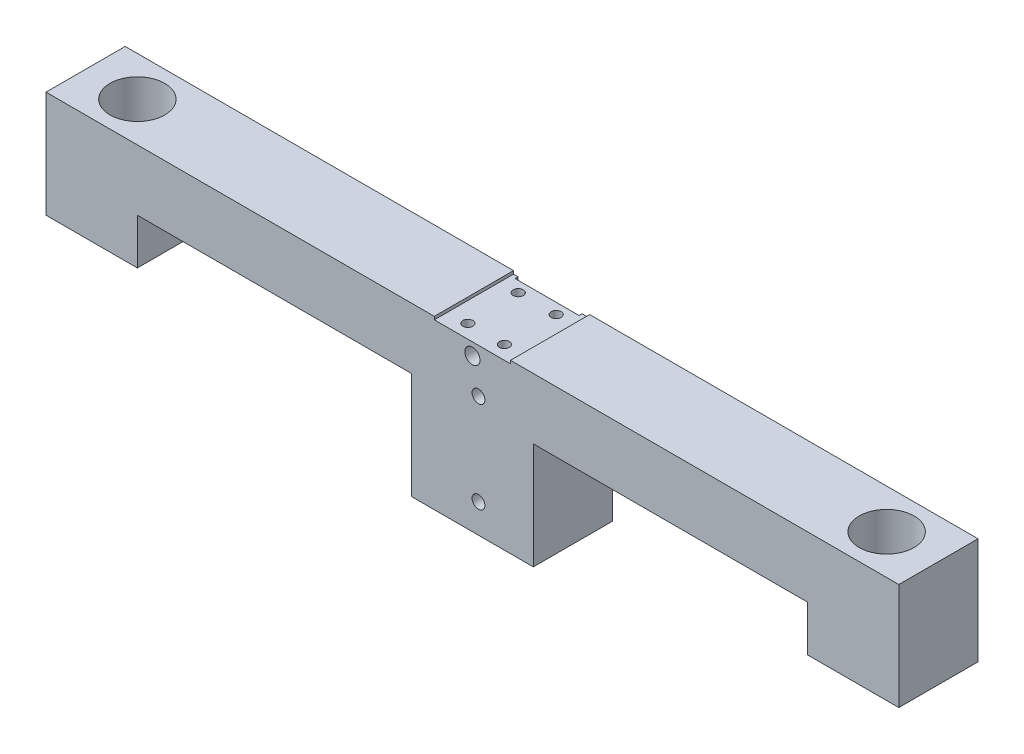
SolidWorks part; units mm, degrees
ref_plane "前视基准面" through (0, 0, 0) normal (0, 0, 1) x (1, 0, 0)
ref_plane "上视基准面" through (0, 0, 0) normal (0, 1, 0) x (1, 0, 0)
ref_plane "右视基准面" through (0, 0, 0) normal (1, 0, 0) x (0, 0, -1)
sketch "草图1" plane through (0, 0, 0) normal (0, 0, 1) x (1, 0, 0)
  line L1 (0, 0) -> (280, 0)
  line L2 (0, 0) -> (0, 35)
  line L3 (0, 35) -> (280, 35)
  line L4 (280, 0) -> (280, 35)
  dimension "D1" = 280
  dimension "D2" = 35
extrude "凸台-拉伸1" add sketch "草图1" along normal blind 26
sketch "草图3" plane through (0, 0, 0) normal (0, -1, 0) x (1, 0, 0)
  line L0 (0, 13) -> (280, 13) construction
  line L1 (0, 26) -> (0, 0) construction
  line L2 (280, 26) -> (280, 0) construction
  line L3 (280, 13) -> (140, 13) construction
  line L4 (140, 13) -> (140, -29.0433) construction
  circle A0 centre (17, 13) radius 9
  circle A1 centre (263, 13) radius 9
  dimension "D1" = 18
  dimension "D2" = 246
extrude "切除-拉伸1" cut sketch "草图3" against normal through all
sketch "草图4" plane through (0, 35, 0) normal (0, 1, 0) x (1, 0, 0)
  line L0 (140, -26) -> (140, 0) construction
  line L1 (280, -26) -> (0, -26) construction
  line L2 (280, 0) -> (0, 0) construction
  line L4 (152.5, -26) -> (127.5, -26)
  line L5 (152.5, -26) -> (152.5, 0)
  line L6 (152.5, 0) -> (127.5, 0)
  line L7 (127.5, -26) -> (127.5, 0)
  dimension "D1" = 25
extrude "切除-拉伸2" cut sketch "草图4" against normal blind 1
hole_wizard "M4 螺纹孔1" positions "草图5" profile "草图6" tap size "M4" standard "ISO"
sketch "草图5" plane through (0, 34, 0) normal (0, 1, 0) x (1, 0, 0)
  point P0 (146, -21.5)
  point P3 (134, -21.5)
  point P6 (146, -4.5)
  point P9 (133.547, -4.5)
sketch "草图6" plane through (146, 34, 21.5) normal (1, 0, 0) x (0, 0, 1)
  line L0 (0, 0) -> (0, 11.0914)
  line L1 (0, 11.0914) -> (1.65, 10.1)
  line L2 (1.65, 10.1) -> (1.65, 0)
  line L5 (1.65, 0) -> (0, 0)
  line L10 (0, 11.0914) -> (-1.65, 10.1) construction
  line L11 (0, -6.35) -> (0, 107.95) construction
  dimension "螺纹孔钻头直径" = 3.3
  dimension "螺纹孔钻头深度" = 10.1
  dimension "导头角度" = 118
cosmetic thread "孔螺蚊线1" parameters "D1"=8, "D2"=4
cosmetic thread "孔螺蚊线2" parameters "D1"=8, "D2"=4
cosmetic thread "孔螺蚊线3" parameters "D1"=8, "D2"=4
cosmetic thread "孔螺蚊线4" parameters "D1"=8, "D2"=4
sketch "草图7" plane through (0, 0, 26) normal (0, 0, 1) x (1, 0, 0)
  line L0 (140, 0) -> (140, 47.7529) construction
  line L1 (0, 0) -> (280, 0) construction
  line L3 (250, 0) -> (30, 0)
  line L4 (250, 0) -> (250, 15)
  line L5 (250, 15) -> (30, 15)
  line L6 (30, 0) -> (30, 15)
  dimension "D1" = 220
  dimension "D2" = 15
extrude "切除-拉伸3" cut sketch "草图7" against normal through all
sketch "草图8" plane through (0, 15, 0) normal (0, -1, 0) x (1, 0, 0)
  line L0 (140, 0) -> (140, 26) construction
  line L1 (250, 0) -> (30, 0) construction
  line L2 (250, 26) -> (30, 26) construction
  line L4 (160, 0) -> (120, 0)
  line L5 (160, 0) -> (160, 26)
  line L6 (160, 26) -> (120, 26)
  line L7 (120, 0) -> (120, 26)
  dimension "D1" = 40
extrude "凸台-拉伸2" add sketch "草图8" along normal blind 35
sketch "草图9" plane through (0, 0, 0) normal (0, 0, -1) x (-1, 0, 0)
  line L0 (-140, -20) -> (-140, 46.0998) construction
  line L1 (-120, -20) -> (-160, -20) construction
  line L3 (-130, -20) -> (-150, -20)
  line L4 (-130, -20) -> (-130, 51.2646)
  line L5 (-130, 51.2646) -> (-150, 51.2646)
  line L6 (-150, -20) -> (-150, 51.2646)
  dimension "D1" = 20
extrude "切除-拉伸4" cut sketch "草图9" against normal blind 1
sketch "草图10" plane through (0, 0, 1) normal (0, 0, -1) x (-1, 0, 0)
  line L0 (-140, -20) -> (-140, 34) construction
  line L1 (-150, -20) -> (-130, -20) construction
  line L2 (-150, 34) -> (-130, 34) construction
  circle A0 centre (-140, 30) radius 2.5
  dimension "D1" = 5
  dimension "D2" = 4
extrude "切除-拉伸5" cut sketch "草图10" against normal through all
sketch "草图12" plane through (130, 0, 0) normal (1, 0, 0) x (0, 0, -1)
  line L1 (-1, 34) -> (0, 34)
  line L2 (-1, 34) -> (-1, -20)
  line L3 (-1, -20) -> (0, -20)
  line L4 (0, 34) -> (0, -20)
extrude "切除-拉伸6" cut sketch "草图12" against normal blind 1
hole_wizard "M5 螺纹孔1" positions "草图13" profile "草图14" tap size "M5" standard "ISO" end condition through all
sketch "草图13" plane through (0, 0, 1) normal (0, 0, -1) x (-1, 0, 0)
  point P0 (-142, -10.5)
  point P3 (-142, 19.5)
sketch "草图14" plane through (142, -10.5, 1) normal (1, 0, 0) x (0, 1, 0)
  line L0 (0, 0) -> (0, 25)
  line L1 (0, 25) -> (2.1, 25)
  line L2 (2.1, 25) -> (2.1, 0)
  line L5 (2.1, 0) -> (0, 0)
  line L11 (0, -6.35) -> (0, 107.95) construction
  dimension "通孔螺纹孔钻头直径" = 4.2
  dimension "通孔螺纹孔钻头深度" = 25
cosmetic thread "孔螺蚊线5" parameters "D2"=5
cosmetic thread "孔螺蚊线6" parameters "D2"=5
